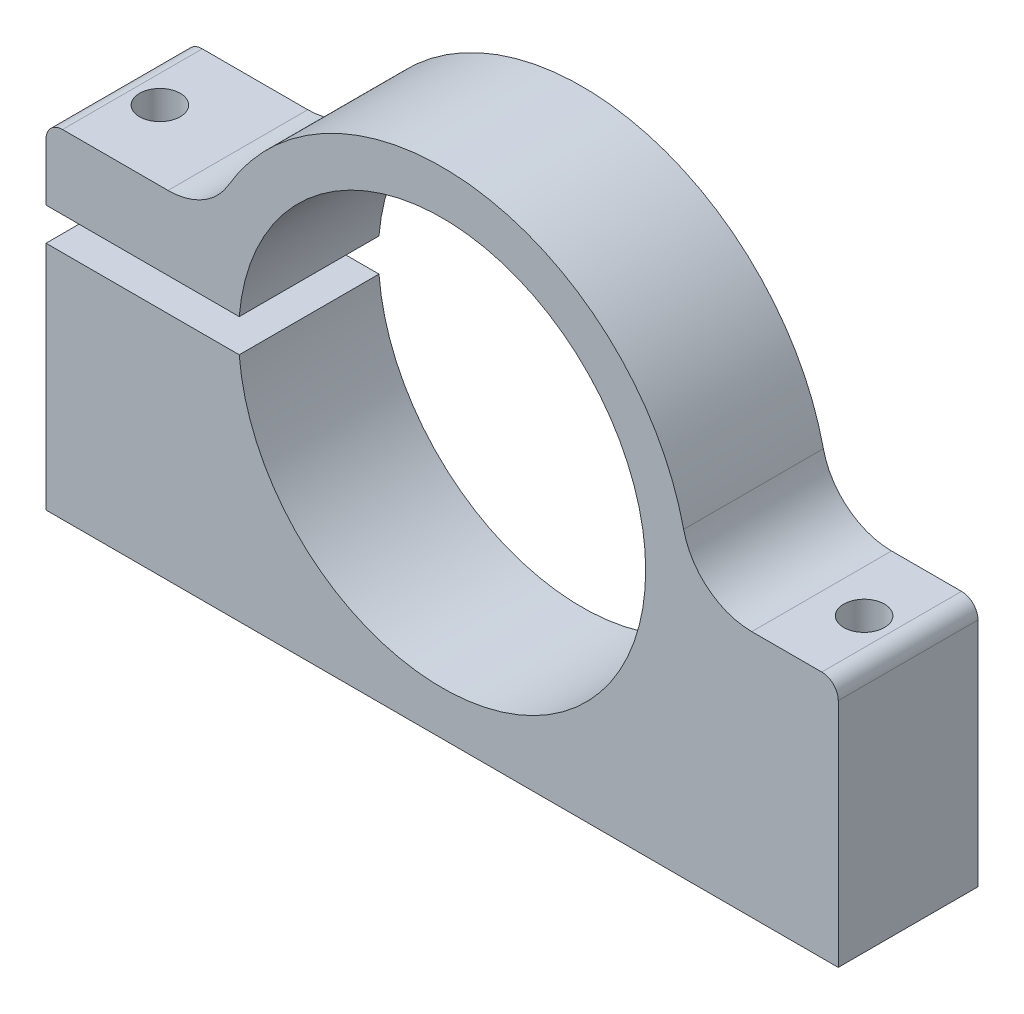
SolidWorks part; units mm, degrees
material "2024 Alloy"
ref_plane "Front Plane" through (0, 0, 0) normal (0, 0, 1) x (1, 0, 0)
ref_plane "Top Plane" through (0, 0, 0) normal (0, 1, 0) x (1, 0, 0)
ref_plane "Right Plane" through (0, 0, 0) normal (1, 0, 0) x (0, 0, -1)
ref_plane "Plane1" through (0, 0, 6.35) normal (0, 0, 1) x (1, 0, 0)
sketch "Sketch1" plane through (0, 0, 6.35) normal (0, 0, 1) x (1, 0, 0)
  line L0 (-20.9526, 8.2) -> (-36, 8.2)
  line L1 (-36, 8.2) -> (-36, -22.5)
  line L2 (-36, -22.5) -> (36, -22.5)
  line L3 (36, -22.5) -> (36, 0)
  line L4 (36, 0) -> (22.5, 0)
  arc A0 (22.5, 0) -> (-20.9526, 8.2) centre (0, 0) ccw
extrude "Boss-Extrude1" add sketch "Sketch1" against normal blind 12.7
sketch "Sketch2" plane through (0, 0, -6.35) normal (0, 0, -1) x (-1, 0, 0)
  line L0 (36, 1.5) -> (18.4391, 1.5)
  line L1 (18.4391, -1.5) -> (36, -1.5)
  line L2 (36, -1.5) -> (36, 1.5)
  arc A0 (18.4391, 1.5) -> (18.4391, -1.5) centre (0, 0) cw
extrude "Cut-Extrude1" cut sketch "Sketch2" against normal through all
sketch "Sketch3" plane through (0, 0, 0) normal (0, 1, 0) x (1, 0, 0)
  line L0 (18.5, 6.35) -> (0, 6.35)
  line L1 (0, 6.35) -> (0, -6.35)
  line L2 (0, -6.35) -> (18.5, -6.35)
  line L3 (18.5, -6.35) -> (18.5, 6.35)
  line L4 (0, 6.35) -> (0, -6.35) construction
revolve "Cut-Revolve1" cut sketch "Sketch3" angle 360 about L4 reverse direction yes
hole_wizard "Ø3.7 (3.7) Diameter Hole1" positions "Sketch5" profile "Sketch4" hole size "Ø3.7" standard "ANSI Metric"
sketch "Sketch5" plane through (0, 8.2, 0) normal (0, 1, 0) x (1, 0, 0)
  point P0 (-32, 0)
sketch "Sketch4" plane through (-32, 8.2, 0) normal (1, 0, 0) x (0, 0, 1)
  line L0 (0, 0) -> (0, 6.7)
  line L1 (0, 6.7) -> (1.85, 6.7)
  line L2 (1.85, 6.7) -> (1.85, 0)
  line L5 (1.85, 0) -> (0, 0)
  line L11 (0, -6.35) -> (0, 107.95) construction
  dimension "Thru Hole Dia." = 3.7
  dimension "Thru Hole Depth" = 6.7
hole_wizard "Ø3.7 (3.7) Diameter Hole2" positions "Sketch7" profile "Sketch6" hole size "Ø3.7" standard "ANSI Metric"
sketch "Sketch7" plane through (0, -22.5, 0) normal (0, -1, 0) x (-1, 0, 0)
  point P0 (32, 0)
sketch "Sketch6" plane through (-32, -22.5, 0) normal (1, 0, 0) x (0, 0, -1)
  line L0 (0, 0) -> (0, 45)
  line L1 (0, 45) -> (1.85, 45)
  line L2 (1.85, 45) -> (1.85, 0)
  line L5 (1.85, 0) -> (0, 0)
  line L11 (0, -6.35) -> (0, 107.95) construction
  dimension "Thru Hole Dia." = 3.7
  dimension "Thru Hole Depth" = 45
hole_wizard "Ø3.7 (3.7) Diameter Hole3" positions "Sketch9" profile "Sketch8" hole size "Ø3.7" standard "ANSI Metric"
sketch "Sketch9" plane through (0, -22.5, 0) normal (0, -1, 0) x (-1, 0, 0)
  point P0 (-32, 0)
sketch "Sketch8" plane through (32, -22.5, 0) normal (1, 0, 0) x (0, 0, -1)
  line L0 (0, 0) -> (0, 45)
  line L1 (0, 45) -> (1.85, 45)
  line L2 (1.85, 45) -> (1.85, 0)
  line L5 (1.85, 0) -> (0, 0)
  line L11 (0, -6.35) -> (0, 107.95) construction
  dimension "Thru Hole Dia." = 3.7
  dimension "Thru Hole Depth" = 45
fillet "Fillet1" radius 1.5 2 edges at (-36, 8.2, 0) (36, 0, 0) tangent propagation no
fillet "Fillet2" radius 6.35 2 edges at (-20.9526, 8.2, 0) (22.5, 0, 0) tangent propagation no
